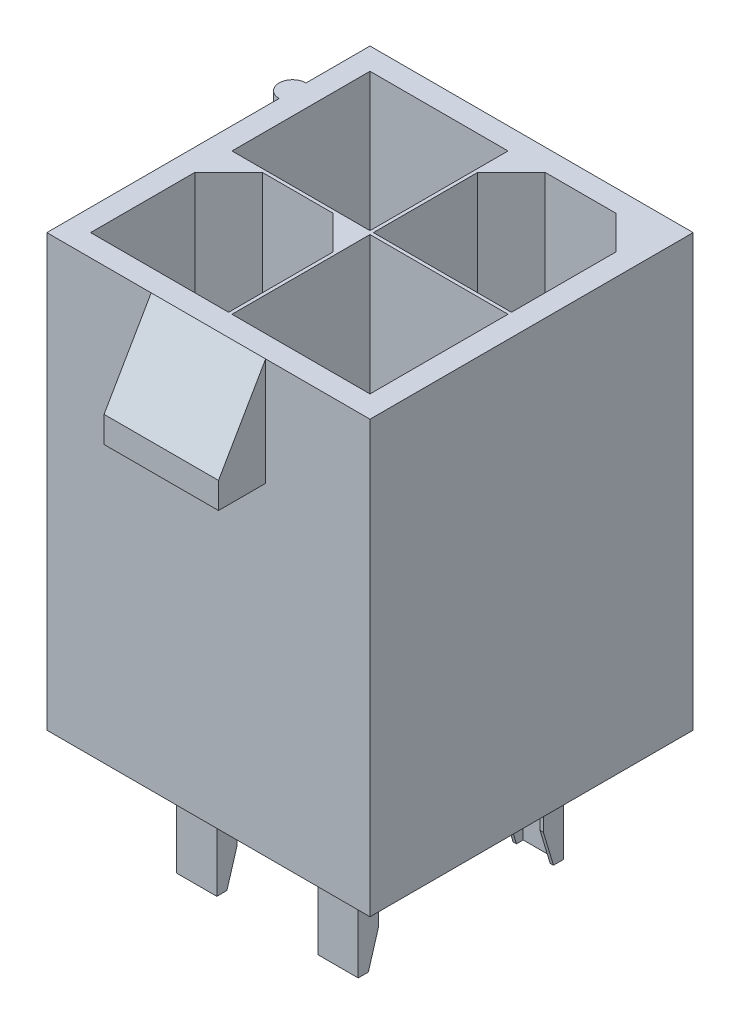
SolidWorks part; units mm, degrees
ref_plane "Спереди" through (0, 0, 0) normal (0, 0, 1) x (1, 0, 0)
ref_plane "Сверху" through (0, 0, 0) normal (0, 1, 0) x (1, 0, 0)
ref_plane "Справа" through (0, 0, 0) normal (1, 0, 0) x (0, 0, -1)
sketch "Эскиз1" plane through (0, 0, 0) normal (0, 1, 0) x (1, 0, 0)
  line L8 (0, -4.0285) -> (0, 8.2994) construction
  line L9 (-2.7, 4.2) -> (-2.7, -2.7)
  line L16 (-2.7, 6.9) -> (6.9, 6.9)
  line L17 (-2.7, 6.9) -> (-2.7, 5)
  line L18 (-2.7, -2.7) -> (6.9, -2.7)
  line L19 (6.9, 6.9) -> (6.9, -2.7)
  arc A0 (-2.7, 4.2) -> (-2.7, 5) centre (-2.7, 4.6) cw
  dimension "D8" = 0.4
  dimension "D5" = 9.6
  dimension "D6" = 9.6
  dimension "D1" = 2.7
  dimension "D2" = 2.3
  dimension "D3" = 2.7
extrude "Housing" add sketch "Эскиз1" along normal blind 12.8
sketch "Эскиз2" plane through (0, 12.8, 0) normal (0, 1, 0) x (1, 0, 0)
  line L0 (-2.05, -2.05) -> (-2.05, 1.05)
  line L1 (-2.05, 1.05) -> (-1.05, 2.05)
  line L2 (-1.05, 2.05) -> (1.05, 2.05)
  line L3 (1.05, 2.05) -> (2.05, 1.05)
  line L4 (2.05, 1.05) -> (2.05, -2.05)
  line L5 (2.05, -2.05) -> (-2.05, -2.05)
  line L6 (0, -2.05) -> (0, 2.05) construction
  line L9 (-2.7, -2.7) -> (6.9, -2.7) construction
  point P10 (0, 0)
  dimension "D2" = 1
  dimension "D3" = 4.1
  dimension "D1" = 4.1
  dimension "D4" = 2.7
sketch "Эскиз3" plane through (0, 12.8, 0) normal (0, 1, 0) x (1, 0, 0)
  line L0 (-2.05, -2.05) -> (-2.05, 1.05) construction
  line L1 (-2.05, 2.15) -> (2.05, 2.15)
  line L2 (-2.05, 2.15) -> (-2.05, 6.25)
  line L3 (-2.05, 6.25) -> (2.05, 6.25)
  line L4 (2.05, 2.15) -> (2.05, 6.25)
  line L6 (-2.05, 4.2) -> (2.05, 4.2) construction
  line L8 (6.9, 6.9) -> (-2.7, 6.9) construction
  point P10 (0, 4.2)
  dimension "D1" = 4.1
  dimension "D2" = 2.7
extrude "Вырез-Вытянуть3" cut sketch "Эскиз2" against normal blind 9.3
extrude "Вырез-Вытянуть4" cut sketch "Эскиз3" against normal blind 9.3
pattern_linear "Линейный массив1" count 2 spacing 4.2 along (1, 0, 0) count 2 spacing 4.2 along (0, 0, 1) skipping (0, 1), (1, 0) of "Вырез-Вытянуть4"
pattern_linear "Линейный массив2" count 2 spacing 4.2 along (1, 0, 0) count 2 spacing 4.2 along (0, 0, -1) skipping (0, 1), (1, 0) of "Вырез-Вытянуть3"
sketch "Эскиз4" plane through (0, 3.5, 0) normal (0, 1, 0) x (1, 0, 0)
  line L0 (0, -3.1521) -> (0, 7.2724) construction
  line L1 (-0.5, 0.5) -> (0.5, 0.5)
  line L2 (-0.5, 0.5) -> (-0.5, -0.5)
  line L3 (-0.5, -0.5) -> (0.5, -0.5)
  line L4 (0.5, 0.5) -> (0.5, -0.5)
  line L5 (-0.5, 0.5) -> (0.5, -0.5) construction
  line L6 (-0.5, -0.5) -> (0.5, 0.5) construction
  line L7 (-0.5, 4.7) -> (0.5, 4.7)
  line L8 (-0.5, 4.7) -> (-0.5, 3.7)
  line L9 (-0.5, 3.7) -> (0.5, 3.7)
  line L10 (0.5, 4.7) -> (0.5, 3.7)
  line L11 (-0.5, 4.7) -> (0.5, 3.7) construction
  line L12 (-0.5, 3.7) -> (0.5, 4.7) construction
  point P0 (0, 0)
  point P9 (0, 4.2)
  dimension "D1" = 1
  dimension "D3" = 4.2
  dimension "D2" = 2
extrude "Контакты" add sketch "Эскиз4" along normal blind 6
chamfer "Фаска1" distance 0.5 angle 45 8 edges at (0, 9.5, -3.7) (-0.5, 9.5, -4.2) (0, 9.5, -4.7) (0.5, 9.5, -4.2) (0, 9.5, 0.5) (-0.5, 9.5, 0) (0, 9.5, -0.5) (0.5, 9.5, 0)
pattern_linear "Линейный массив3" count 2 spacing 4.2 along (1, 0, 0) of "Контакты", "Фаска1"
sketch "Эскиз5" plane through (-2.7, 0, 0) normal (-1, 0, 0) x (0, 0, 1)
  line L0 (2.7, 12.8) -> (2.7, 0) construction
  line L1 (-4.2, 12.8) -> (2.7, 12.8) construction
  line L9 (2.7, 9.6) -> (2.7, 12.8)
  line L10 (4.1, 9.6) -> (2.7, 9.6)
  line L11 (4.1, 10.3751) -> (4.1, 9.6)
  line L12 (2.7, 12.8) -> (4.1, 10.3751)
  dimension "D1" = 1.4
  dimension "D2" = 3.2
  dimension "D3" = 60
extrude "Фиксатор" add sketch "Эскиз5" along direction (-1, 0, 0) on the side against the normal blind 3.4 from offset 3.1 offset against normal yes
sketch "Эскиз6" plane through (0, 0, 0) normal (0, -1, 0) x (1, 0, 0)
  line L0 (-0.6, -4.55) -> (-0.6, -5.15)
  line L1 (-0.6, -5.15) -> (0.6, -5.15)
  line L2 (0.6, -5.15) -> (0.6, -4.55)
  line L3 (0.6, -4.55) -> (0.5, -4.55)
  line L4 (0.5, -4.55) -> (0.5, -5.05)
  line L5 (0.5, -5.05) -> (-0.5, -5.05)
  line L6 (-0.5, -5.05) -> (-0.5, -4.55)
  line L7 (-0.5, -4.55) -> (-0.6, -4.55)
  line L8 (6.9, -2.1) -> (-2.7, -2.1) construction
  line L9 (6.9, 2.7) -> (6.9, -6.9) construction
  line L10 (-2.7, -4.2) -> (-2.7, 2.7) construction
  line L11 (-2.7, -6.9) -> (-2.7, -5) construction
  line L12 (-0.5, 0.35) -> (-0.6, 0.35)
  line L13 (-0.5, 0.85) -> (-0.5, 0.35)
  line L14 (0.5, 0.85) -> (-0.5, 0.85)
  line L15 (0.5, 0.35) -> (0.5, 0.85)
  line L16 (0.6, 0.35) -> (0.5, 0.35)
  line L17 (0.6, 0.95) -> (0.6, 0.35)
  line L18 (-0.6, 0.95) -> (0.6, 0.95)
  line L19 (-0.6, 0.35) -> (-0.6, 0.95)
  dimension "D1" = 0.1
  dimension "D2" = 0.1
  dimension "D3" = 1.2
  dimension "D4" = 2.1
  dimension "D5" = 0.6
  dimension "D6" = 5.5
extrude "Выводы" add sketch "Эскиз6" along normal blind 3.5
sketch "Эскиз7" plane through (0.6, 0, 0) normal (1, 0, 0) x (0, 0, -1)
  line L0 (-0.65, -3.5) -> (-0.35, -2.5)
  line L1 (-0.35, -3.5) -> (-0.95, -3.5) construction
  line L2 (-0.35, -3.5) -> (-0.35, 0) construction
  line L3 (-0.35, -2.5) -> (4.55, -2.5)
  line L4 (4.55, -3.5) -> (4.55, 0) construction
  line L5 (4.55, -2.5) -> (4.85, -3.5)
  line L6 (5.15, -3.5) -> (4.55, -3.5) construction
  line L7 (4.85, -3.5) -> (-0.65, -3.5)
  dimension "D1" = 1
extrude "Вырез-Вытянуть5" cut sketch "Эскиз7" against normal blind 1.25
pattern_linear "Линейный массив4" count 2 spacing 4.2 along (1, 0, 0) of "Выводы", "Вырез-Вытянуть5"
sketch "Origin_ref" plane through (0, 0, 0) normal (0, -1, 0) x (1, 0, 0)
  line L0 (0, -4.2) -> (0, -8.7004) construction
  line L3 (0, -4.2) -> (2.9828, -4.2) construction
  point P0 (0, -4.2)
equation "\"D3@Эскиз2\"=\"D1@Эскиз2\""
equation "\"D1@Эскиз3\"=\"D1@Эскиз2\""
equation "\"D19@Фиксатор\"=(\"D6@Эскиз1\"-3.4)/2"
